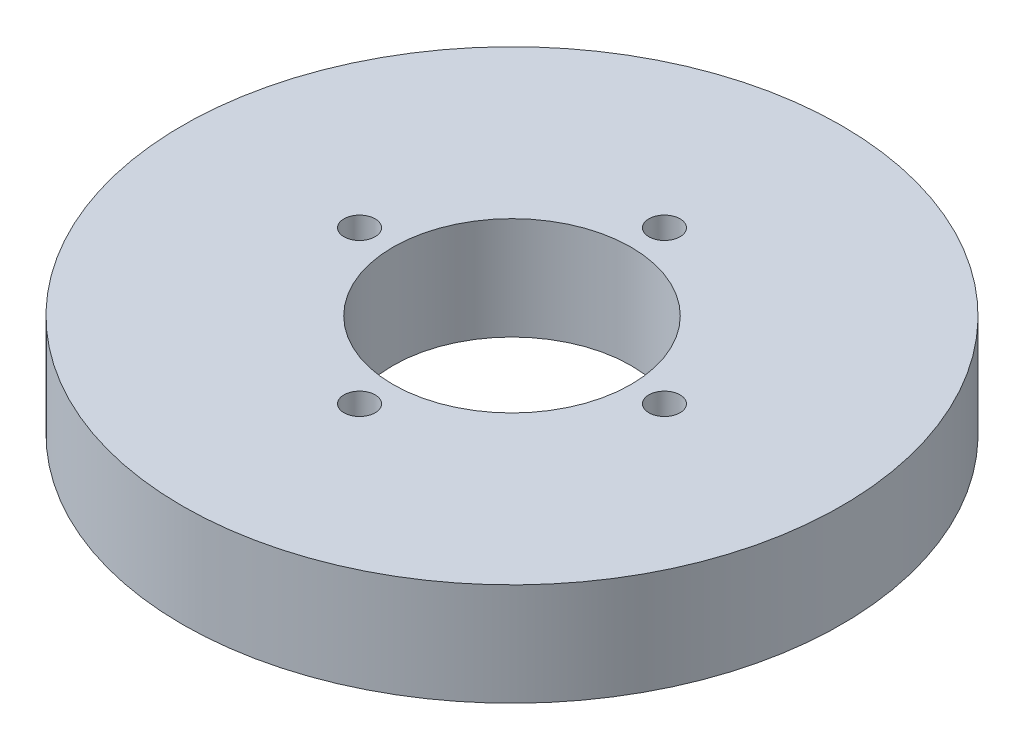
SolidWorks part; units mm, degrees
ref_plane "Front Plane" through (0, 0, 0) normal (0, 0, 1) x (1, 0, 0)
ref_plane "Top Plane" through (0, 0, 0) normal (0, 1, 0) x (1, 0, 0)
ref_plane "Right Plane" through (0, 0, 0) normal (1, 0, 0) x (0, 0, -1)
sketch "Sketch1" plane through (0, 0, 0) normal (0, 1, 0) x (1, 0, 0)
  circle A0 centre (0, 0) radius 90
  dimension "FLANGE_OD" = 180
extrude "Boss-Extrude1" add sketch "Sketch1" along normal blind 28
sketch "Sketch2" plane through (0, 0, 0) normal (0, 1, 0) x (1, 0, 0)
  circle A0 centre (0, 0) radius 32.5
  dimension "BORE_D" = 65
extrude "Cut-Extrude1" cut sketch "Sketch2" along normal through all
sketch "Sketch3" plane through (0, 28, 0) normal (0, 1, 0) x (1, 0, 0)
  circle A0 centre (0, 0) radius 41.6326 construction
  circle A1 centre (-41.6326, 0) radius 4.2559
  dimension "BOLT_D" = 8.5117
  dimension "BOLT_PCD" = 83.2651
extrude "Cut-Extrude2" cut sketch "Sketch3" against normal blind 18.9302
pattern_circular "CirPattern1" count 4 over 360 about axis through (0, 0, 0) along (0, 1, 0) of "Cut-Extrude2"
